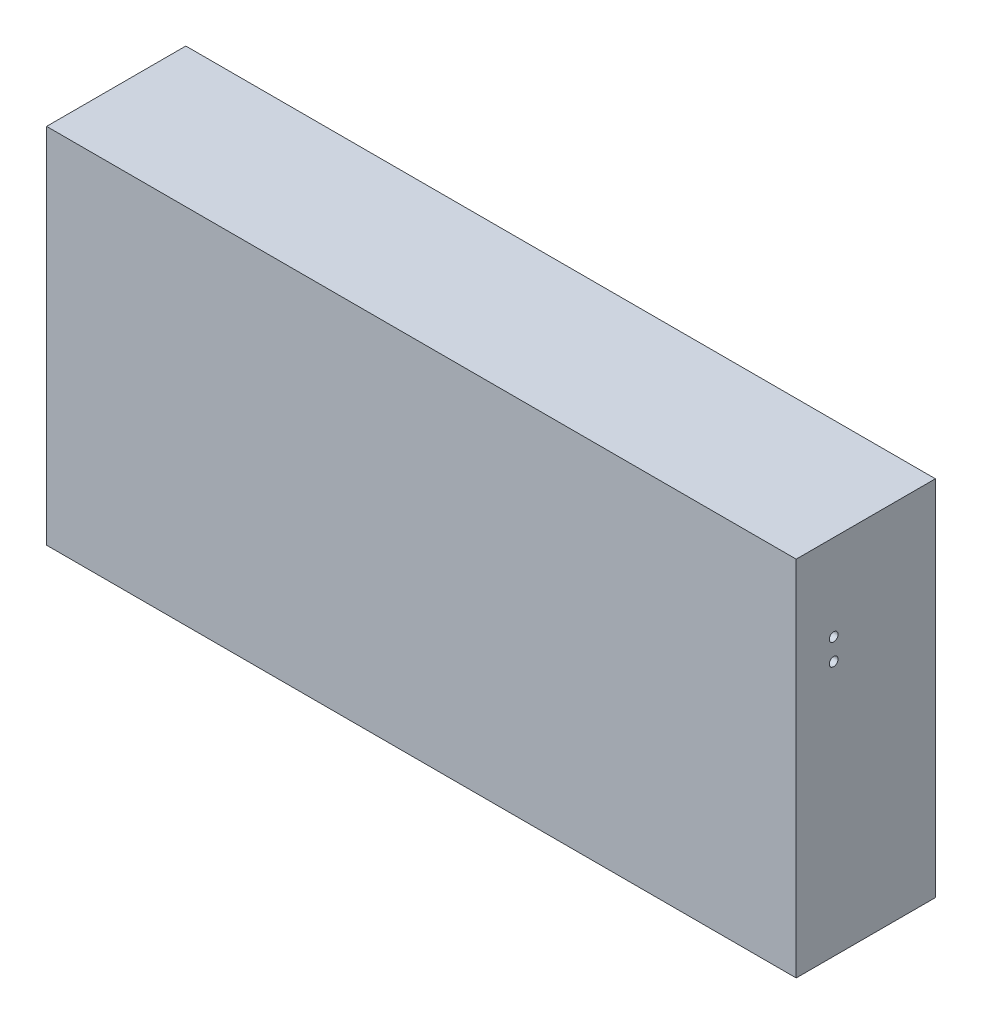
SolidWorks part; units mm, degrees
ref_plane "Front Plane" through (0, 0, 0) normal (0, 0, 1) x (1, 0, 0)
ref_plane "Top Plane" through (0, 0, 0) normal (0, 1, 0) x (1, 0, 0)
ref_plane "Right Plane" through (0, 0, 0) normal (1, 0, 0) x (0, 0, -1)
ref_plane "Plane1" through (0, 135, 0) normal (0, -1, 0) x (1, 0, 0)
sketch "Sketch1" plane through (0, 135, 0) normal (0, -1, 0) x (1, 0, 0)
  line L0 (0, 9) -> (280, 9)
  line L1 (280, 9) -> (280, 61)
  line L2 (280, 61) -> (0, 61)
  line L3 (0, 61) -> (0, 9)
extrude "Tapa frontal" add sketch "Sketch1" against normal blind 3
sketch "Sketch2" plane through (0, 135, 0) normal (0, -1, 0) x (1, 0, 0)
  line L0 (271.25, 9) -> (271.25, 17)
  line L1 (271.25, 17) -> (277, 22.75)
  line L2 (277, 22.75) -> (277, 58)
  line L3 (277, 58) -> (141.5, 58)
  line L4 (141.5, 58) -> (141.5, 24.25)
  line L5 (141.5, 24.25) -> (148.75, 17)
  line L6 (148.75, 17) -> (148.75, 9)
  line L7 (148.75, 9) -> (131.25, 9)
  line L8 (131.25, 9) -> (131.25, 17)
  line L9 (131.25, 17) -> (138.5, 24.25)
  line L10 (138.5, 24.25) -> (138.5, 58)
  line L11 (138.5, 58) -> (3, 58)
  line L12 (3, 58) -> (3, 22.75)
  line L13 (3, 22.75) -> (8.75, 17)
  line L14 (8.75, 17) -> (8.75, 9)
  line L15 (8.75, 9) -> (0, 9)
  line L16 (0, 9) -> (0, 61)
  line L17 (0, 61) -> (280, 61)
  line L18 (280, 61) -> (280, 9)
  line L19 (280, 9) -> (271.25, 9)
extrude "Venas apoyo" add sketch "Sketch2" along normal blind 129
sketch "Sketch3" plane through (0, 6, 0) normal (0, -1, 0) x (1, 0, 0)
  line L0 (280, 61) -> (280, 9)
  line L1 (280, 9) -> (0, 9)
  line L2 (0, 9) -> (0, 61)
  line L3 (0, 61) -> (280, 61)
extrude "Placa unión" add sketch "Sketch3" along normal blind 3.5
sketch "Sketch9" plane through (138.5, 0, 0) normal (-1, 0, 0) x (0, 0, 1)
  line L0 (55, 62) -> (55, 76)
  line L1 (29, 76) -> (29, 62)
  arc A0 (55, 76) -> (29, 76) centre (42, 76) ccw
  arc A1 (29, 62) -> (55, 62) centre (42, 62) ccw
extrude "Cut-Extrude4" cut sketch "Sketch9" against normal up to next
sketch "Sketch10" plane through (0, 6, 0) normal (0, 1, 0) x (-1, 0, 0)
  line L0 (-81, 21) -> (-59, 21)
  line L1 (-59, 43) -> (-81, 43)
  line L3 (-280, 61) -> (0, 61) construction
  line L4 (-199, 43) -> (-221, 43)
  line L5 (-221, 21) -> (-199, 21)
  arc A0 (-81, 43) -> (-81, 21) centre (-81, 32) ccw
  arc A1 (-59, 21) -> (-59, 43) centre (-59, 32) ccw
  arc A2 (-199, 21) -> (-199, 43) centre (-199, 32) ccw
  arc A3 (-221, 43) -> (-221, 21) centre (-221, 32) ccw
  dimension "D2" = 11
  dimension "D1" = 22
  dimension "D3" = 18
  dimension "D4" = 2
extrude "Cut-Extrude5" cut sketch "Sketch10" against normal through all
hole_wizard "Ø4.3 (4.3) Diameter Hole1" positions "Sketch13" profile "Sketch12" hole size "Ø4.3" standard "ANSI Metric" end condition through all
sketch "Sketch13" plane through (0, 6, 0) normal (0, 1, 0) x (1, 0, 0)
  point P0 (245, -46)
  point P1 (175, -46)
  point P2 (245, -20)
  point P3 (175, -20)
  point P4 (105, -46)
  point P5 (35, -46)
  point P6 (105, -20)
  point P7 (35, -20)
sketch "Sketch12" plane through (245, 6, 46) normal (1, 0, 0) x (0, 0, 1)
  line L0 (0, 0) -> (0, 3.5)
  line L1 (0, 3.5) -> (2.15, 3.5)
  line L2 (2.15, 3.5) -> (2.15, 0)
  line L5 (2.15, 0) -> (0, 0)
  line L11 (0, -6.35) -> (0, 107.95) construction
  dimension "Thru Hole Dia." = 4.3
  dimension "Thru Hole Depth" = 3.5
hole_wizard "Ø2.5 (3) Diameter Hole1" positions "Sketch15" profile "Sketch14" hole size "Ø2.5" standard "ANSI Metric"
sketch "Sketch15" plane through (0, 0, 9) normal (0, 0, -1) x (-1, 0, 0)
  point P0 (-275.5, 126)
  point P1 (-144.5, 126)
  point P2 (-275.5, 104)
  point P3 (-275.5, 82)
  point P4 (-144.5, 104)
  point P5 (-144.5, 82)
  point P6 (-135.5, 126)
  point P7 (-4.5, 126)
  point P8 (-135.5, 104)
  point P9 (-135.5, 82)
  point P10 (-4.5, 104)
  point P11 (-4.5, 82)
  point P12 (-275.5, 60)
  point P13 (-144.5, 60)
  point P14 (-275.5, 38)
  point P15 (-275.5, 16)
  point P16 (-144.5, 38)
  point P17 (-144.5, 16)
  point P18 (-135.5, 60)
  point P19 (-4.5, 60)
  point P20 (-135.5, 38)
  point P21 (-135.5, 16)
  point P22 (-4.5, 38)
  point P23 (-4.5, 16)
sketch "Sketch14" plane through (275.5, 126, 9) normal (1, 0, 0) x (0, 1, 0)
  line L0 (0, 0) -> (0, 10)
  line L1 (0, 10) -> (1.5, 10)
  line L2 (1.5, 10) -> (1.5, 0)
  line L5 (1.5, 0) -> (0, 0)
  line L10 (0, 10) -> (-1.5, 10) construction
  line L11 (0, -6.35) -> (0, 107.95) construction
  dimension "Hole Dia." = 3
  dimension "Hole Depth" = 10
  dimension "Drill Angle" = 180
sketch "Sketch16" plane through (0, 0, 61) normal (0, 0, 1) x (1, 0, 0)
  line L5 (280, 138) -> (280, 2.5) construction
  line L6 (280, 104) -> (295, 104)
  line L7 (280, 104) -> (280, 86)
  line L8 (280, 86) -> (295, 86)
  line L9 (298, 101) -> (298, 89)
  line L10 (140, 138) -> (140, 3.7181) construction
  line L11 (280, 138) -> (0, 138) construction
  line L12 (280, 138) -> (0, 138) construction
  line L13 (-18, 101) -> (-18, 89)
  line L14 (0, 86) -> (-15, 86)
  line L15 (0, 104) -> (0, 86)
  line L16 (0, 104) -> (-15, 104)
  circle A0 centre (290.3818, 95) radius 3.15
  circle A1 centre (-10.3818, 95) radius 3.15
  arc A2 (295, 86) -> (298, 89) centre (295, 89) ccw
  arc A3 (295, 104) -> (298, 101) centre (295, 101) cw
  arc A4 (-18, 89) -> (-15, 86) centre (-15, 89) ccw
  arc A5 (-18, 101) -> (-15, 104) centre (-15, 101) cw
  point P22 (298, 95)
  point P27 (298, 86)
  point P30 (298, 104)
  point P33 (-18, 86)
  point P36 (-18, 104)
  dimension "D3" = 6.3
  dimension "D5" = 3
  dimension "D6" = 3
  dimension "D1" = 18
  dimension "D2" = 18
  dimension "D4" = 34
extrude "Anclajes" [suppressed] add sketch "Sketch16" against normal blind 4
sketch "Sketch17" plane through (0, 0, 58) normal (0, 0, -1) x (-1, 0, 0)
  circle A0 centre (-238.9223, 87.46) radius 3
  circle A1 centre (-238.9223, 87.46) radius 1.5
  circle A2 centre (-238.9223, 51.154) radius 3
  circle A3 centre (-238.9223, 51.154) radius 1.5
  circle A4 centre (-184.6933, 51.154) radius 3
  circle A5 centre (-184.6933, 51.154) radius 1.5
  circle A6 centre (-184.6933, 87.46) radius 3
  circle A7 centre (-184.6933, 87.46) radius 1.5
  circle A8 centre (-96.5374, 87.46) radius 3
  circle A9 centre (-96.5374, 87.46) radius 1.5
  circle A10 centre (-42.3084, 87.46) radius 3
  circle A11 centre (-42.3084, 87.46) radius 1.5
  circle A12 centre (-42.3084, 51.154) radius 3
  circle A13 centre (-42.3084, 51.154) radius 1.5
  circle A14 centre (-96.5374, 51.154) radius 3
  circle A15 centre (-96.5374, 51.154) radius 1.5
  dimension "D1" = 6
  dimension "D2" = 3
extrude "Boss-Extrude1" add sketch "Sketch17" along normal blind 5
fillet "Fillet1" radius 3 8 edges at (45.3084, 51.154, 58) (45.3084, 87.46, 58) (99.5374, 51.154, 58) (99.5374, 87.46, 58) (241.9223, 87.46, 58) (187.6933, 87.46, 58) (187.6933, 51.154, 58) (241.9223, 51.154, 58)
fillet "Fillet2" [suppressed] radius 5
sketch "Sketch18" plane through (0, 0, 0) normal (-1, 0, 0) x (0, 0, 1)
  circle A0 centre (47, 105.8568) radius 1.65
  circle A1 centre (47, 97.8568) radius 1.65
  dimension "D1" = 3.3
extrude "Cut-Extrude6" cut sketch "Sketch18" against normal through all
